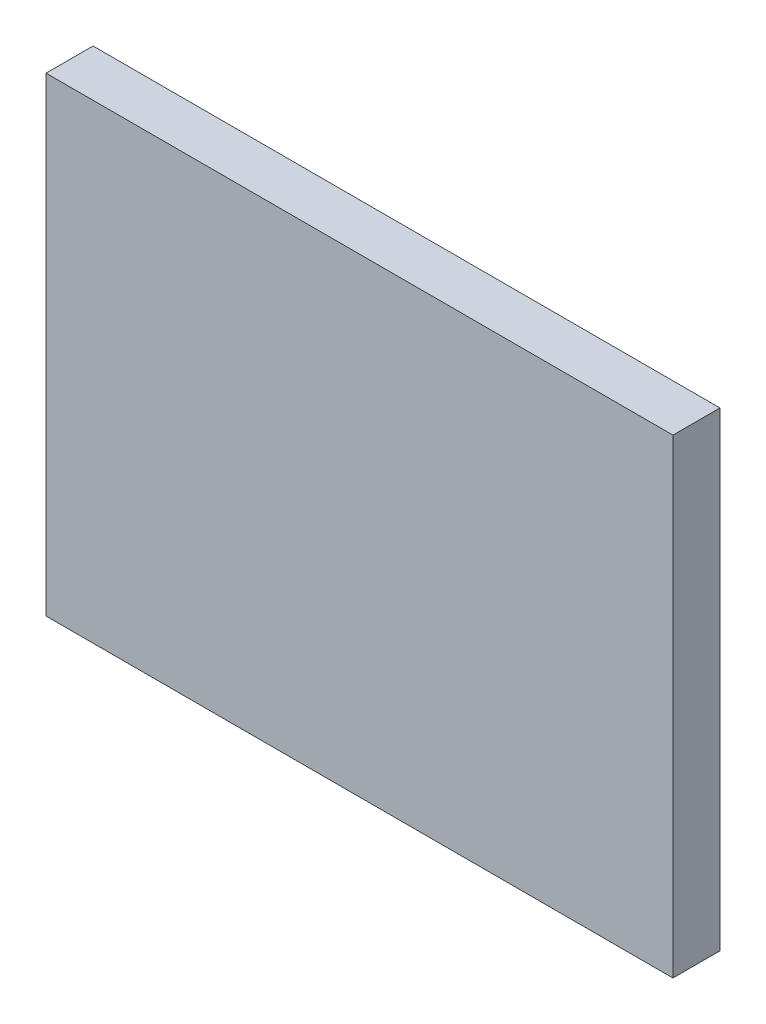
SolidWorks part; units mm, degrees
ref_plane "前视基准面" through (0, 0, 0) normal (0, 0, 1) x (1, 0, 0)
ref_plane "上视基准面" through (0, 0, 0) normal (0, 1, 0) x (1, 0, 0)
ref_plane "右视基准面" through (0, 0, 0) normal (1, 0, 0) x (0, 0, -1)
other "Configuration Table"
sketch "草图1" plane through (0, 0, 0) normal (0, 0, 1) x (1, 0, 0)
  line L1 (-200, -150) -> (200, -150)
  line L2 (-200, -150) -> (-200, 150)
  line L3 (-200, 150) -> (200, 150)
  line L4 (200, -150) -> (200, 150)
  line L5 (-200, -150) -> (200, 150) construction
  line L6 (-200, 150) -> (200, -150) construction
  point P0 (0, 0)
  dimension "D1" = 400
  dimension "D2" = 300
extrude "凸台-拉伸1" add sketch "草图1" along normal blind 30
sketch "草图2" plane through (0, 0, 0) normal (0, 0, -1) x (-1, 0, 0)
  circle A0 centre (0, 0) radius 40
extrude "凸台-拉伸2" add sketch "草图2" along normal blind 10 contours A0
sketch "草图3" plane through (0, 0, 0) normal (0, 0, -1) x (-1, 0, 0)
  line L0 (193.1805, 31.2414) -> (193.1805, -39.3727)
  line L1 (193.1805, 31.2414) -> (121.9153, 31.2414)
  line L2 (193.1805, -39.3727) -> (121.9153, -39.3727)
  line L3 (121.9153, 31.2414) -> (121.9153, -39.3727)
extrude "凸台-拉伸3" add sketch "草图3" along normal blind 70
sketch "草图4" plane through (-121.9153, 0, 0) normal (1, 0, 0) x (0, 0, -1)
  line L0 (0, -4.0657) -> (45, -4.0657) construction
  circle A0 centre (45, -4.0657) radius 5
  dimension "D3" = 10
  dimension "D2" = 45
extrude "凸台-拉伸4" add sketch "草图4" along normal blind 15
sketch "草图5" plane through (-193.1805, 0, 0) normal (-1, 0, 0) x (0, 0, 1)
  line L0 (-70, -39.3727) -> (0, -39.3727) construction
  line L1 (0, -39.3727) -> (0, 31.2414) construction
  line L2 (-64.371, 31.2414) -> (-70, 31.2414)
  line L3 (-70, -35.9775) -> (-70, -39.3727)
  line L4 (0, -39.3727) -> (0, 31.2414)
  line L5 (0, 31.2414) -> (-70, 31.2414)
  line L6 (-70, 31.2414) -> (-70, -39.3727)
  line L7 (-70, -39.3727) -> (0, -39.3727)
  line L8 (0, -39.3727) -> (0, -35.3429)
  line L9 (0, 31.2414) -> (-6.3844, 31.2414)
  line L10 (-70, 31.2414) -> (-70, 25.6123)
  line L11 (-70, -39.3727) -> (-66.6048, -39.3727)
  line L12 (0, 24.8569) -> (0, 31.2414)
  arc A0 (-70, 25.6123) -> (-64.371, 31.2414) centre (-64.371, 25.6123) cw
  arc A1 (-6.3844, 31.2414) -> (0, 24.8569) centre (-6.3844, 24.8569) cw
  arc A2 (-70, -35.9775) -> (-66.6048, -39.3727) centre (-66.6048, -35.9775) ccw
  arc A3 (0, -35.3429) -> (-3.8632, -39.3692) centre (-4.0298, -35.3429) cw
  dimension "D1" = 0
fillet "圆角1" radius 10 4 edges at (-157.5479, 31.2414, 0) (-157.5479, -39.3727, 0) (-157.5479, -39.3727, -70) (-157.5479, 31.2414, -70)
sketch "草图6" plane through (-121.9153, 0, 0) normal (1, 0, 0) x (0, 0, -1)
  circle A2 centre (45, -4.0657) radius 15.4448
extrude "凸台-拉伸5" add sketch "草图6" along normal blind 6
chamfer "倒角1" distance 6 angle 45 1 edges at (-115.9153, -4.0657, -60.4448)
